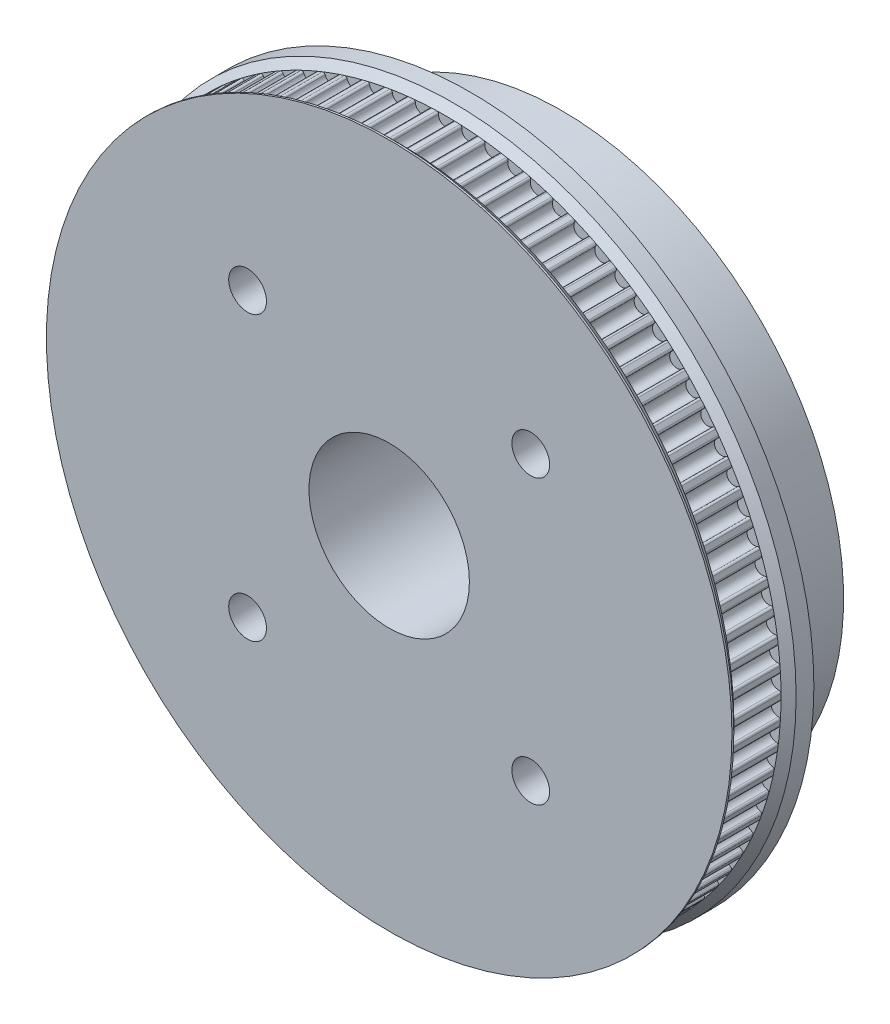
SolidWorks part; units mm, degrees
ref_plane "Front Plane" through (0, 0, 0) normal (0, 0, 1) x (1, 0, 0)
ref_plane "Top Plane" through (0, 0, 0) normal (0, 1, 0) x (1, 0, 0)
ref_plane "Right Plane" through (0, 0, 0) normal (1, 0, 0) x (0, 0, -1)
sketch "Sketch1" plane through (0, 0, 0) normal (0, 0, 1) x (1, 0, 0)
  line L0 (0, 71.6197) -> (0, 0) construction
  line L1 (0, 0) -> (4.9959, 71.4453) construction
  line L2 (0, 70.4947) -> (1.9534, 70.5727) construction
  line L3 (2.9742, 70.537) -> (4.9175, 70.323) construction
  line L4 (1.9534, 70.5727) -> (1.9653, 71.0025) construction
  line L5 (2.9742, 70.537) -> (2.9923, 70.9667) construction
  arc A0 (0, 71.6197) -> (4.9959, 71.4453) centre (0, 0) cw construction
  circle A1 centre (0, 0) radius 71.6197 construction
  circle A2 centre (0, 0) radius 71.0297
  circle A3 centre (0, 0) radius 68.9697
  circle A8 centre (0, 0) radius 72.7697 construction
  circle A9 centre (0, 70.4947) radius 1.525
  circle A10 centre (4.9175, 70.323) radius 1.525
  circle A11 centre (1.9534, 70.5727) radius 0.43
  circle A12 centre (2.9742, 70.537) radius 0.43
  point P18 (0, 68.9697)
  point P19 (4.2572, 15.8881)
  point P20 (4.2572, 15.8881)
  point P21 (1.5238, 70.5555)
  point P23 (3.4016, 70.49)
  dimension "D6" = 3.05
  dimension "D7" = 3.05
  dimension "D8" = 0.86
  dimension "D9" = 0.86
  dimension "D5" = 3.8
  dimension "D2" = 5
  dimension "D3" = 0.59
  dimension "D4" = 2.06
extrude "Boss-Extrude1" add sketch "Sketch1" along normal blind 10 contours A2
extrude "Cut-Extrude1" cut sketch "Sketch1<5>" along normal through all contours A11 A2 A9 | A12 A10 A2 | A9 | A10 region at (3.3605, 70.8449, 0) region at (1.5896, 70.9067, 0)
sketch "Sketch1<5>" plane through (0, 0, 0) normal (0, 0, 1) x (1, 0, 0) same geometry as "Sketch1"
pattern_circular "CirPattern3" count 90 over 360 about axis through (0, 0, 10) along (0, 0, 1) of "Cut-Extrude1"
sketch "Sketch2" plane through (0, 0, 10) normal (0, 0, 1) x (1, 0, 0)
  circle A0 centre (0, 0) radius 72.7697 construction
  arc A81 (-46.5195, 53.0692) -> (-44.1849, 55.0282) centre (-45.3131, 54.0021) ccw
  arc A82 (-46.5195, 53.0692) -> (-44.1849, 55.0282) centre (-45.3131, 54.0021) ccw
  arc A83 (-46.5195, 53.0692) -> (-47.1451, 53.1278) centre (-46.8597, 52.8062) ccw
  arc A84 (-46.5195, 53.0692) -> (-47.1451, 53.1278) centre (-46.8597, 52.8062) ccw
  arc A85 (-47.1451, 53.1278) -> (-47.9088, 52.4402) centre (0, 0) ccw
  arc A86 (-47.1451, 53.1278) -> (-47.9088, 52.4402) centre (0, 0) ccw
  arc A87 (-47.9088, 52.4402) -> (-47.9159, 51.8119) centre (-47.6187, 52.1227) ccw
  arc A88 (-47.9088, 52.4402) -> (-47.9159, 51.8119) centre (-47.6187, 52.1227) ccw
  arc A89 (-50.1081, 49.6949) -> (-47.9159, 51.8119) centre (-48.9698, 50.7097) ccw
  arc A90 (-50.1081, 49.6949) -> (-47.9159, 51.8119) centre (-48.9698, 50.7097) ccw
  arc A91 (-50.1081, 49.6949) -> (-50.7363, 49.7097) centre (-50.4291, 49.4088) ccw
  arc A92 (-50.1081, 49.6949) -> (-50.7363, 49.7097) centre (-50.4291, 49.4088) ccw
  arc A93 (-50.7363, 49.7097) -> (-51.4501, 48.9705) centre (0, 0) ccw
  arc A95 (-50.7363, 49.7097) -> (-51.4501, 48.9705) centre (0, 0) ccw
  arc A97 (-51.4501, 48.9705) -> (-51.4134, 48.3433) centre (-51.1386, 48.674) ccw
  arc A99 (-51.4501, 48.9705) -> (-51.4134, 48.3433) centre (-51.1386, 48.674) ccw
  arc A101 (-53.4526, 46.0785) -> (-51.4134, 48.3433) centre (-52.3878, 47.1702) ccw
  arc A103 (-53.4526, 46.0785) -> (-51.4134, 48.3433) centre (-52.3878, 47.1702) ccw
  arc A105 (-53.4526, 46.0785) -> (-54.0802, 46.0494) centre (-53.7528, 45.7707) ccw
  arc A107 (-53.4526, 46.0785) -> (-54.0802, 46.0494) centre (-53.7528, 45.7707) ccw
  arc A109 (-54.0802, 46.0494) -> (-54.7408, 45.2622) centre (0, 0) ccw
  arc A111 (-54.0802, 46.0494) -> (-54.7408, 45.2622) centre (0, 0) ccw
  arc A112 (-54.7408, 45.2622) -> (-54.6604, 44.6391) centre (-54.4094, 44.9882) ccw
  arc A114 (-54.7408, 45.2622) -> (-54.6604, 44.6391) centre (-54.4094, 44.9882) ccw
  arc A116 (-56.5367, 42.2376) -> (-54.6604, 44.6391) centre (-55.5506, 43.4009) ccw
  arc A118 (-56.5367, 42.2376) -> (-54.6604, 44.6391) centre (-55.5506, 43.4009) ccw
  arc A122 (-56.5367, 42.2376) -> (-57.1607, 42.1648) centre (-56.8147, 41.9096) ccw
  arc A126 (-56.5367, 42.2376) -> (-57.1607, 42.1648) centre (-56.8147, 41.9096) ccw
  arc A130 (-57.1607, 42.1648) -> (-57.7648, 41.3335) centre (0, 0) ccw
  arc A134 (-57.1607, 42.1648) -> (-57.7648, 41.3335) centre (0, 0) ccw
  arc A138 (-57.7648, 41.3335) -> (-57.6411, 40.7174) centre (-57.4151, 41.0832) ccw
  arc A142 (-57.7648, 41.3335) -> (-57.6411, 40.7174) centre (-57.4151, 41.0832) ccw
  arc A146 (-59.3453, 38.1909) -> (-57.6411, 40.7174) centre (-58.4428, 39.4201) ccw
  arc A150 (-59.3453, 38.1909) -> (-57.6411, 40.7174) centre (-58.4428, 39.4201) ccw
  arc A154 (-59.3453, 38.1909) -> (-59.9628, 38.0748) centre (-59.5998, 37.8443) ccw
  arc A158 (-59.3453, 38.1909) -> (-59.9628, 38.0748) centre (-59.5998, 37.8443) ccw
  arc A162 (-59.9628, 38.0748) -> (-60.5073, 37.2033) centre (0, 0) ccw
  arc A166 (-59.9628, 38.0748) -> (-60.5073, 37.2033) centre (0, 0) ccw
  arc A170 (-60.5073, 37.2033) -> (-60.341, 36.5974) centre (-60.141, 36.9781) ccw
  arc A174 (-60.5073, 37.2033) -> (-60.341, 36.5974) centre (-60.141, 36.9781) ccw
  arc A178 (-61.8648, 33.9581) -> (-60.341, 36.5974) centre (-61.0502, 35.2474) ccw
  arc A182 (-61.8648, 33.9581) -> (-60.341, 36.5974) centre (-61.0502, 35.2474) ccw
  arc A186 (-61.8648, 33.9581) -> (-62.4727, 33.7992) centre (-62.0945, 33.5946) ccw
  arc A190 (-61.8648, 33.9581) -> (-62.4727, 33.7992) centre (-62.0945, 33.5946) ccw
  arc A193 (-62.4727, 33.7992) -> (-62.9551, 32.8919) centre (0, 0) ccw
  arc A195 (-62.4727, 33.7992) -> (-62.9551, 32.8919) centre (0, 0) ccw
  arc A197 (-62.9551, 32.8919) -> (-62.7469, 32.2991) centre (-62.574, 32.6928) ccw
  arc A199 (-62.9551, 32.8919) -> (-62.7469, 32.2991) centre (-62.574, 32.6928) ccw
  arc A201 (-64.0829, 29.5599) -> (-62.7469, 32.2991) centre (-63.3602, 30.9029) ccw
  arc A203 (-64.0829, 29.5599) -> (-62.7469, 32.2991) centre (-63.3602, 30.9029) ccw
  arc A205 (-64.0829, 29.5599) -> (-64.6782, 29.359) centre (-64.2867, 29.1813) ccw
  arc A207 (-64.0829, 29.5599) -> (-64.6782, 29.359) centre (-64.2867, 29.1813) ccw
  arc A209 (-64.6782, 29.359) -> (-65.0962, 28.4202) centre (0, 0) ccw
  arc A211 (-64.6782, 29.359) -> (-65.0962, 28.4202) centre (0, 0) ccw
  arc A213 (-65.0962, 28.4202) -> (-64.8471, 27.8434) centre (-64.7021, 28.2482) ccw
  arc A215 (-65.0962, 28.4202) -> (-64.8471, 27.8434) centre (-64.7021, 28.2482) ccw
  arc A217 (-65.9888, 25.0177) -> (-64.8471, 27.8434) centre (-65.3616, 26.4078) ccw
  arc A221 (-65.9888, 25.0177) -> (-64.8471, 27.8434) centre (-65.3616, 26.4078) ccw
  arc A225 (-65.9888, 25.0177) -> (-66.5686, 24.7758) centre (-66.1656, 24.6258) ccw
  arc A229 (-65.9888, 25.0177) -> (-66.5686, 24.7758) centre (-66.1656, 24.6258) ccw
  arc A233 (-66.5686, 24.7758) -> (-66.9201, 23.8101) centre (0, 0) ccw
  arc A241 (-66.5686, 24.7758) -> (-66.9201, 23.8101) centre (0, 0) ccw
  arc A245 (-66.9201, 23.8101) -> (-66.6314, 23.2521) centre (-66.515, 23.666) ccw
  arc A247 (-66.9201, 23.8101) -> (-66.6314, 23.2521) centre (-66.515, 23.666) ccw
  arc A249 (-67.5732, 20.3537) -> (-66.6314, 23.2521) centre (-67.0445, 21.7841) ccw
  arc A251 (-67.5732, 20.3537) -> (-66.6314, 23.2521) centre (-67.0445, 21.7841) ccw
  arc A253 (-67.5732, 20.3537) -> (-68.1347, 20.0718) centre (-67.7223, 19.9503) ccw
  arc A255 (-67.5732, 20.3537) -> (-68.1347, 20.0718) centre (-67.7223, 19.9503) ccw
  arc A257 (-68.1347, 20.0718) -> (-68.418, 19.084) centre (0, 0) ccw
  arc A259 (-68.1347, 20.0718) -> (-68.418, 19.084) centre (0, 0) ccw
  arc A261 (-68.418, 19.084) -> (-68.0911, 18.5475) centre (-68.0038, 18.9685) ccw
  arc A263 (-68.418, 19.084) -> (-68.0911, 18.5475) centre (-68.0038, 18.9685) ccw
  arc A373 (3.4016, 70.49) -> (6.4418, 70.2774) centre (4.9175, 70.323) ccw
  arc A374 (3.4016, 70.49) -> (2.9923, 70.9667) centre (2.9742, 70.537) ccw
  arc A375 (2.9923, 70.9667) -> (1.9653, 71.0025) centre (0, 0) ccw
  arc A376 (1.9653, 71.0025) -> (1.5238, 70.5555) centre (1.9534, 70.5727) ccw
  arc A377 (-1.5238, 70.5555) -> (1.5238, 70.5555) centre (0, 70.4947) ccw
  arc A378 (-1.5238, 70.5555) -> (-1.9653, 71.0025) centre (-1.9534, 70.5727) ccw
  arc A379 (-1.9653, 71.0025) -> (-2.9923, 70.9667) centre (0, 0) ccw
  arc A380 (-2.9923, 70.9667) -> (-3.4016, 70.49) centre (-2.9742, 70.537) ccw
  arc A381 (-6.4418, 70.2774) -> (-3.4016, 70.49) centre (-4.9175, 70.323) ccw
  arc A382 (-6.4418, 70.2774) -> (-6.9134, 70.6925) centre (-6.8716, 70.2645) ccw
  arc A383 (-6.9134, 70.6925) -> (-7.9354, 70.5851) centre (0, 0) ccw
  arc A384 (-7.9354, 70.5851) -> (-8.3105, 70.081) centre (-7.8874, 70.1578) ccw
  arc A385 (-11.3284, 69.6568) -> (-8.3105, 70.081) centre (-9.811, 69.8087) ccw
  arc A386 (-11.3284, 69.6568) -> (-11.8279, 70.038) centre (-11.7563, 69.614) ccw
  arc A387 (-11.8279, 70.038) -> (-12.8399, 69.8596) centre (0, 0) ccw
  arc A388 (-12.8399, 69.8596) -> (-13.1788, 69.3305) centre (-12.7621, 69.4367) ccw
  arc A389 (-16.1598, 68.6969) -> (-13.1788, 69.3305) centre (-14.6567, 68.9542) ccw
  arc A390 (-16.1598, 68.6969) -> (-16.6847, 69.0423) centre (-16.5836, 68.6244) ccw
  arc A391 (-16.6847, 69.0423) -> (-17.6817, 68.7937) centre (0, 0) ccw
  arc A392 (-17.6817, 68.7937) -> (-17.983, 68.2424) centre (-17.5747, 68.3773) ccw
  arc A393 (-20.9125, 67.4023) -> (-17.983, 68.2424) centre (-19.431, 67.7639) ccw
  arc A394 (-20.9125, 67.4023) -> (-21.4602, 67.7103) centre (-21.3302, 67.3004) ccw
  arc A395 (-21.4602, 67.7103) -> (-22.4375, 67.3927) centre (0, 0) ccw
  arc A396 (-22.4375, 67.3927) -> (-22.6995, 66.8217) centre (-22.3016, 66.9848) ccw
  arc A397 (-25.5633, 65.7794) -> (-22.6995, 66.8217) centre (-24.1106, 66.2434) ccw
  arc A398 (-25.5633, 65.7794) -> (-26.1311, 66.0484) centre (-25.9729, 65.6485) ccw
  arc A399 (-26.1311, 66.0484) -> (-27.0839, 65.6634) centre (0, 0) ccw
  arc A400 (-27.0839, 65.6634) -> (-27.3055, 65.0755) centre (-26.9199, 65.2659) ccw
  arc A401 (-30.0896, 63.8359) -> (-27.3055, 65.0755) centre (-28.6728, 64.4001) ccw
  arc A402 (-30.0896, 63.8359) -> (-30.6748, 64.0647) centre (-30.4891, 63.6768) ccw
  arc A403 (-30.6748, 64.0647) -> (-31.5984, 63.6142) centre (0, 0) ccw
  arc A404 (-31.5984, 63.6142) -> (-31.7784, 63.0122) centre (-31.4071, 63.2291) ccw
  arc A405 (-34.4692, 61.5815) -> (-31.7784, 63.0122) centre (-33.0953, 62.2431) ccw
  arc A406 (-34.4692, 61.5815) -> (-35.069, 61.7688) centre (-34.8567, 61.3949) ccw
  arc A407 (-35.069, 61.7688) -> (-35.9589, 61.255) centre (0, 0) ccw
  arc A408 (-35.9589, 61.255) -> (-36.0965, 60.642) centre (-35.7412, 60.8842) ccw
  arc A409 (-38.681, 59.027) -> (-36.0965, 60.642) centre (-37.3565, 59.7829) ccw
  arc A410 (-38.681, 59.027) -> (-39.2923, 59.1721) centre (-39.0544, 58.8139) ccw
  arc A411 (-39.2923, 59.1721) -> (-40.1442, 58.5975) centre (0, 0) ccw
  arc A412 (-40.1442, 58.5975) -> (-40.2387, 57.9763) centre (-39.9012, 58.2427) ccw
  arc A413 (-42.7043, 56.185) -> (-40.2387, 57.9763) centre (-41.4358, 57.0314) ccw
  arc A414 (-42.7043, 56.185) -> (-43.3242, 56.2871) centre (-43.062, 55.9463) ccw
  arc A415 (-43.3242, 56.2871) -> (-44.134, 55.6544) centre (0, 0) ccw
  arc A416 (-44.134, 55.6544) -> (-44.1849, 55.0282) centre (-43.8668, 55.3175) ccw
  arc A649 (3.4016, 70.49) -> (6.4418, 70.2774) centre (4.9175, 70.323) ccw
  arc A650 (3.4016, 70.49) -> (2.9923, 70.9667) centre (2.9742, 70.537) ccw
  arc A651 (2.9923, 70.9667) -> (1.9653, 71.0025) centre (0, 0) ccw
  arc A652 (1.9653, 71.0025) -> (1.5238, 70.5555) centre (1.9534, 70.5727) ccw
  arc A653 (-1.5238, 70.5555) -> (1.5238, 70.5555) centre (0, 70.4947) ccw
  arc A654 (-1.5238, 70.5555) -> (-1.9653, 71.0025) centre (-1.9534, 70.5727) ccw
  arc A655 (-1.9653, 71.0025) -> (-2.9923, 70.9667) centre (0, 0) ccw
  arc A656 (-2.9923, 70.9667) -> (-3.4016, 70.49) centre (-2.9742, 70.537) ccw
  arc A657 (-6.4418, 70.2774) -> (-3.4016, 70.49) centre (-4.9175, 70.323) ccw
  arc A658 (-6.4418, 70.2774) -> (-6.9134, 70.6925) centre (-6.8716, 70.2645) ccw
  arc A659 (-6.9134, 70.6925) -> (-7.9354, 70.5851) centre (0, 0) ccw
  arc A660 (-7.9354, 70.5851) -> (-8.3105, 70.081) centre (-7.8874, 70.1578) ccw
  arc A661 (-11.3284, 69.6568) -> (-8.3105, 70.081) centre (-9.811, 69.8087) ccw
  arc A662 (-11.3284, 69.6568) -> (-11.8279, 70.038) centre (-11.7563, 69.614) ccw
  arc A663 (-11.8279, 70.038) -> (-12.8399, 69.8596) centre (0, 0) ccw
  arc A664 (-12.8399, 69.8596) -> (-13.1788, 69.3305) centre (-12.7621, 69.4367) ccw
  arc A665 (-16.1598, 68.6969) -> (-13.1788, 69.3305) centre (-14.6567, 68.9542) ccw
  arc A666 (-16.1598, 68.6969) -> (-16.6847, 69.0423) centre (-16.5836, 68.6244) ccw
  arc A667 (-16.6847, 69.0423) -> (-17.6817, 68.7937) centre (0, 0) ccw
  arc A668 (-17.6817, 68.7937) -> (-17.983, 68.2424) centre (-17.5747, 68.3773) ccw
  arc A669 (-20.9125, 67.4023) -> (-17.983, 68.2424) centre (-19.431, 67.7639) ccw
  arc A670 (-20.9125, 67.4023) -> (-21.4602, 67.7103) centre (-21.3302, 67.3004) ccw
  arc A671 (-21.4602, 67.7103) -> (-22.4375, 67.3927) centre (0, 0) ccw
  arc A672 (-22.4375, 67.3927) -> (-22.6995, 66.8217) centre (-22.3016, 66.9848) ccw
  arc A673 (-25.5633, 65.7794) -> (-22.6995, 66.8217) centre (-24.1106, 66.2434) ccw
  arc A674 (-25.5633, 65.7794) -> (-26.1311, 66.0484) centre (-25.9729, 65.6485) ccw
  arc A675 (-26.1311, 66.0484) -> (-27.0839, 65.6634) centre (0, 0) ccw
  arc A676 (-27.0839, 65.6634) -> (-27.3055, 65.0755) centre (-26.9199, 65.2659) ccw
  arc A677 (-30.0896, 63.8359) -> (-27.3055, 65.0755) centre (-28.6728, 64.4001) ccw
  arc A678 (-30.0896, 63.8359) -> (-30.6748, 64.0647) centre (-30.4891, 63.6768) ccw
  arc A679 (-30.6748, 64.0647) -> (-31.5984, 63.6142) centre (0, 0) ccw
  arc A680 (-31.5984, 63.6142) -> (-31.7784, 63.0122) centre (-31.4071, 63.2291) ccw
  arc A681 (-34.4692, 61.5815) -> (-31.7784, 63.0122) centre (-33.0953, 62.2431) ccw
  arc A682 (-34.4692, 61.5815) -> (-35.069, 61.7688) centre (-34.8567, 61.3949) ccw
  arc A683 (-35.069, 61.7688) -> (-35.9589, 61.255) centre (0, 0) ccw
  arc A684 (-35.9589, 61.255) -> (-36.0965, 60.642) centre (-35.7412, 60.8842) ccw
  arc A685 (-38.681, 59.027) -> (-36.0965, 60.642) centre (-37.3565, 59.7829) ccw
  arc A686 (-38.681, 59.027) -> (-39.2923, 59.1721) centre (-39.0544, 58.8139) ccw
  arc A687 (-39.2923, 59.1721) -> (-40.1442, 58.5975) centre (0, 0) ccw
  arc A688 (-40.1442, 58.5975) -> (-40.2387, 57.9763) centre (-39.9012, 58.2427) ccw
  arc A689 (-42.7043, 56.185) -> (-40.2387, 57.9763) centre (-41.4358, 57.0314) ccw
  arc A690 (-42.7043, 56.185) -> (-43.3242, 56.2871) centre (-43.062, 55.9463) ccw
  arc A691 (-43.3242, 56.2871) -> (-44.134, 55.6544) centre (0, 0) ccw
  arc A692 (-44.134, 55.6544) -> (-44.1849, 55.0282) centre (-43.8668, 55.3175) ccw
  arc A1359 (-6.9134, -70.6925) -> (-6.4418, -70.2774) centre (-6.8716, -70.2645) ccw
  arc A1361 (-6.9134, -70.6925) -> (-6.4418, -70.2774) centre (-6.8716, -70.2645) ccw
  arc A1363 (-3.4016, -70.49) -> (-6.4418, -70.2774) centre (-4.9175, -70.323) ccw
  arc A1365 (-3.4016, -70.49) -> (-6.4418, -70.2774) centre (-4.9175, -70.323) ccw
  arc A1367 (-3.4016, -70.49) -> (-2.9923, -70.9667) centre (-2.9742, -70.537) ccw
  arc A1369 (-3.4016, -70.49) -> (-2.9923, -70.9667) centre (-2.9742, -70.537) ccw
  arc A1371 (-2.9923, -70.9667) -> (-1.9653, -71.0025) centre (0, 0) ccw
  arc A1373 (-2.9923, -70.9667) -> (-1.9653, -71.0025) centre (0, 0) ccw
  arc A1375 (-1.9653, -71.0025) -> (-1.5238, -70.5555) centre (-1.9534, -70.5727) ccw
  arc A1377 (-1.9653, -71.0025) -> (-1.5238, -70.5555) centre (-1.9534, -70.5727) ccw
  arc A1379 (1.5238, -70.5555) -> (-1.5238, -70.5555) centre (0, -70.4947) ccw
  arc A1381 (1.5238, -70.5555) -> (-1.5238, -70.5555) centre (0, -70.4947) ccw
  arc A1383 (1.5238, -70.5555) -> (1.9653, -71.0025) centre (1.9534, -70.5727) ccw
  arc A1385 (1.5238, -70.5555) -> (1.9653, -71.0025) centre (1.9534, -70.5727) ccw
  arc A1387 (1.9653, -71.0025) -> (2.9923, -70.9667) centre (0, 0) ccw
  arc A1389 (1.9653, -71.0025) -> (2.9923, -70.9667) centre (0, 0) ccw
  arc A1391 (2.9923, -70.9667) -> (3.4016, -70.49) centre (2.9742, -70.537) ccw
  arc A1393 (2.9923, -70.9667) -> (3.4016, -70.49) centre (2.9742, -70.537) ccw
  arc A1395 (6.4418, -70.2774) -> (3.4016, -70.49) centre (4.9175, -70.323) ccw
  arc A1397 (6.4418, -70.2774) -> (3.4016, -70.49) centre (4.9175, -70.323) ccw
  arc A1399 (6.4418, -70.2774) -> (6.9134, -70.6925) centre (6.8716, -70.2645) ccw
  arc A1401 (6.4418, -70.2774) -> (6.9134, -70.6925) centre (6.8716, -70.2645) ccw
  arc A1403 (6.9134, -70.6925) -> (7.9354, -70.5851) centre (0, 0) ccw
  arc A1405 (6.9134, -70.6925) -> (7.9354, -70.5851) centre (0, 0) ccw
  arc A1407 (7.9354, -70.5851) -> (8.3105, -70.081) centre (7.8874, -70.1578) ccw
  arc A1409 (7.9354, -70.5851) -> (8.3105, -70.081) centre (7.8874, -70.1578) ccw
  arc A1411 (11.3284, -69.6568) -> (8.3105, -70.081) centre (9.811, -69.8087) ccw
  arc A1413 (11.3284, -69.6568) -> (8.3105, -70.081) centre (9.811, -69.8087) ccw
  arc A1415 (11.3284, -69.6568) -> (11.8279, -70.038) centre (11.7563, -69.614) ccw
  arc A1417 (11.3284, -69.6568) -> (11.8279, -70.038) centre (11.7563, -69.614) ccw
  arc A1419 (11.8279, -70.038) -> (12.8399, -69.8596) centre (0, 0) ccw
  arc A1421 (11.8279, -70.038) -> (12.8399, -69.8596) centre (0, 0) ccw
  arc A1423 (12.8399, -69.8596) -> (13.1788, -69.3305) centre (12.7621, -69.4367) ccw
  arc A1425 (12.8399, -69.8596) -> (13.1788, -69.3305) centre (12.7621, -69.4367) ccw
  arc A1427 (16.1598, -68.6969) -> (13.1788, -69.3305) centre (14.6567, -68.9542) ccw
  arc A1429 (16.1598, -68.6969) -> (13.1788, -69.3305) centre (14.6567, -68.9542) ccw
  arc A1431 (16.1598, -68.6969) -> (16.6847, -69.0423) centre (16.5836, -68.6244) ccw
  arc A1433 (16.1598, -68.6969) -> (16.6847, -69.0423) centre (16.5836, -68.6244) ccw
  arc A1435 (16.6847, -69.0423) -> (17.6817, -68.7937) centre (0, 0) ccw
  arc A1437 (16.6847, -69.0423) -> (17.6817, -68.7937) centre (0, 0) ccw
  arc A1439 (17.6817, -68.7937) -> (17.983, -68.2424) centre (17.5747, -68.3773) ccw
  arc A1441 (17.6817, -68.7937) -> (17.983, -68.2424) centre (17.5747, -68.3773) ccw
  arc A1443 (20.9125, -67.4023) -> (17.983, -68.2424) centre (19.431, -67.7639) ccw
  arc A1445 (20.9125, -67.4023) -> (17.983, -68.2424) centre (19.431, -67.7639) ccw
  arc A1447 (20.9125, -67.4023) -> (21.4602, -67.7103) centre (21.3302, -67.3004) ccw
  arc A1449 (20.9125, -67.4023) -> (21.4602, -67.7103) centre (21.3302, -67.3004) ccw
  arc A1451 (21.4602, -67.7103) -> (22.4375, -67.3927) centre (0, 0) ccw
  arc A1453 (21.4602, -67.7103) -> (22.4375, -67.3927) centre (0, 0) ccw
  arc A1455 (22.4375, -67.3927) -> (22.6995, -66.8217) centre (22.3016, -66.9848) ccw
  arc A1457 (22.4375, -67.3927) -> (22.6995, -66.8217) centre (22.3016, -66.9848) ccw
  arc A1459 (25.5633, -65.7794) -> (22.6995, -66.8217) centre (24.1106, -66.2434) ccw
  arc A1461 (25.5633, -65.7794) -> (22.6995, -66.8217) centre (24.1106, -66.2434) ccw
  arc A1463 (25.5633, -65.7794) -> (26.1311, -66.0484) centre (25.9729, -65.6485) ccw
  arc A1465 (25.5633, -65.7794) -> (26.1311, -66.0484) centre (25.9729, -65.6485) ccw
  arc A1467 (26.1311, -66.0484) -> (27.0839, -65.6634) centre (0, 0) ccw
  arc A1469 (26.1311, -66.0484) -> (27.0839, -65.6634) centre (0, 0) ccw
  arc A1471 (27.0839, -65.6634) -> (27.3055, -65.0755) centre (26.9199, -65.2659) ccw
  arc A1473 (27.0839, -65.6634) -> (27.3055, -65.0755) centre (26.9199, -65.2659) ccw
  arc A1475 (30.0896, -63.8359) -> (27.3055, -65.0755) centre (28.6728, -64.4001) ccw
  arc A1477 (30.0896, -63.8359) -> (27.3055, -65.0755) centre (28.6728, -64.4001) ccw
  arc A1479 (30.0896, -63.8359) -> (30.6748, -64.0647) centre (30.4891, -63.6768) ccw
  arc A1481 (30.0896, -63.8359) -> (30.6748, -64.0647) centre (30.4891, -63.6768) ccw
  arc A1483 (30.6748, -64.0647) -> (31.5984, -63.6142) centre (0, 0) ccw
  arc A1485 (30.6748, -64.0647) -> (31.5984, -63.6142) centre (0, 0) ccw
  arc A1487 (31.5984, -63.6142) -> (31.7784, -63.0122) centre (31.4071, -63.2291) ccw
  arc A1489 (31.5984, -63.6142) -> (31.7784, -63.0122) centre (31.4071, -63.2291) ccw
  arc A1491 (34.4692, -61.5815) -> (31.7784, -63.0122) centre (33.0953, -62.2431) ccw
  arc A1493 (34.4692, -61.5815) -> (31.7784, -63.0122) centre (33.0953, -62.2431) ccw
  arc A1495 (34.4692, -61.5815) -> (35.069, -61.7688) centre (34.8567, -61.3949) ccw
  arc A1497 (34.4692, -61.5815) -> (35.069, -61.7688) centre (34.8567, -61.3949) ccw
  arc A1499 (35.069, -61.7688) -> (35.9589, -61.255) centre (0, 0) ccw
  arc A1501 (35.069, -61.7688) -> (35.9589, -61.255) centre (0, 0) ccw
  arc A1503 (35.9589, -61.255) -> (36.0965, -60.642) centre (35.7412, -60.8842) ccw
  arc A1505 (35.9589, -61.255) -> (36.0965, -60.642) centre (35.7412, -60.8842) ccw
  arc A1507 (38.681, -59.027) -> (36.0965, -60.642) centre (37.3565, -59.7829) ccw
  arc A1509 (38.681, -59.027) -> (36.0965, -60.642) centre (37.3565, -59.7829) ccw
  arc A1511 (38.681, -59.027) -> (39.2923, -59.1721) centre (39.0544, -58.8139) ccw
  arc A1513 (38.681, -59.027) -> (39.2923, -59.1721) centre (39.0544, -58.8139) ccw
  arc A1515 (39.2923, -59.1721) -> (40.1442, -58.5975) centre (0, 0) ccw
  arc A1517 (39.2923, -59.1721) -> (40.1442, -58.5975) centre (0, 0) ccw
  arc A1519 (40.1442, -58.5975) -> (40.2387, -57.9763) centre (39.9012, -58.2427) ccw
  arc A1521 (40.1442, -58.5975) -> (40.2387, -57.9763) centre (39.9012, -58.2427) ccw
  arc A1523 (42.7043, -56.185) -> (40.2387, -57.9763) centre (41.4358, -57.0314) ccw
  arc A1525 (42.7043, -56.185) -> (40.2387, -57.9763) centre (41.4358, -57.0314) ccw
  arc A1527 (42.7043, -56.185) -> (43.3242, -56.2871) centre (43.062, -55.9463) ccw
  arc A1529 (42.7043, -56.185) -> (43.3242, -56.2871) centre (43.062, -55.9463) ccw
  arc A1531 (43.3242, -56.2871) -> (44.134, -55.6544) centre (0, 0) ccw
  arc A1533 (43.3242, -56.2871) -> (44.134, -55.6544) centre (0, 0) ccw
  arc A1535 (44.134, -55.6544) -> (44.1849, -55.0282) centre (43.8668, -55.3175) ccw
  arc A1537 (44.134, -55.6544) -> (44.1849, -55.0282) centre (43.8668, -55.3175) ccw
  arc A1539 (46.5195, -53.0692) -> (44.1849, -55.0282) centre (45.3131, -54.0021) ccw
  arc A1541 (46.5195, -53.0692) -> (44.1849, -55.0282) centre (45.3131, -54.0021) ccw
  arc A1543 (46.5195, -53.0692) -> (47.1451, -53.1278) centre (46.8597, -52.8062) ccw
  arc A1545 (46.5195, -53.0692) -> (47.1451, -53.1278) centre (46.8597, -52.8062) ccw
  arc A1547 (47.1451, -53.1278) -> (47.9088, -52.4402) centre (0, 0) ccw
  arc A1549 (47.1451, -53.1278) -> (47.9088, -52.4402) centre (0, 0) ccw
  arc A1551 (47.9088, -52.4402) -> (47.9159, -51.8119) centre (47.6187, -52.1227) ccw
  arc A1553 (47.9088, -52.4402) -> (47.9159, -51.8119) centre (47.6187, -52.1227) ccw
  arc A1555 (50.1081, -49.6949) -> (47.9159, -51.8119) centre (48.9698, -50.7097) ccw
  arc A1557 (50.1081, -49.6949) -> (47.9159, -51.8119) centre (48.9698, -50.7097) ccw
  arc A1559 (50.1081, -49.6949) -> (50.7363, -49.7097) centre (50.4291, -49.4088) ccw
  arc A1561 (50.1081, -49.6949) -> (50.7363, -49.7097) centre (50.4291, -49.4088) ccw
  arc A1563 (50.7363, -49.7097) -> (51.4501, -48.9705) centre (0, 0) ccw
  arc A1565 (50.7363, -49.7097) -> (51.4501, -48.9705) centre (0, 0) ccw
  arc A1567 (51.4501, -48.9705) -> (51.4134, -48.3433) centre (51.1386, -48.674) ccw
  arc A1569 (51.4501, -48.9705) -> (51.4134, -48.3433) centre (51.1386, -48.674) ccw
  arc A1571 (53.4526, -46.0785) -> (51.4134, -48.3433) centre (52.3878, -47.1702) ccw
  arc A1573 (53.4526, -46.0785) -> (51.4134, -48.3433) centre (52.3878, -47.1702) ccw
  arc A1575 (53.4526, -46.0785) -> (54.0802, -46.0494) centre (53.7528, -45.7707) ccw
  arc A1577 (53.4526, -46.0785) -> (54.0802, -46.0494) centre (53.7528, -45.7707) ccw
  arc A1579 (54.0802, -46.0494) -> (54.7408, -45.2622) centre (0, 0) ccw
  arc A1581 (54.0802, -46.0494) -> (54.7408, -45.2622) centre (0, 0) ccw
  arc A1583 (54.7408, -45.2622) -> (54.6604, -44.6391) centre (54.4094, -44.9882) ccw
  arc A1585 (54.7408, -45.2622) -> (54.6604, -44.6391) centre (54.4094, -44.9882) ccw
  arc A1587 (56.5367, -42.2376) -> (54.6604, -44.6391) centre (55.5506, -43.4009) ccw
  arc A1589 (56.5367, -42.2376) -> (54.6604, -44.6391) centre (55.5506, -43.4009) ccw
  arc A1591 (56.5367, -42.2376) -> (57.1607, -42.1648) centre (56.8147, -41.9096) ccw
  arc A1593 (56.5367, -42.2376) -> (57.1607, -42.1648) centre (56.8147, -41.9096) ccw
  arc A1595 (57.1607, -42.1648) -> (57.7648, -41.3335) centre (0, 0) ccw
  arc A1596 (57.1607, -42.1648) -> (57.7648, -41.3335) centre (0, 0) ccw
  arc A1597 (57.7648, -41.3335) -> (57.6411, -40.7174) centre (57.4151, -41.0832) ccw
  arc A1598 (57.7648, -41.3335) -> (57.6411, -40.7174) centre (57.4151, -41.0832) ccw
  arc A1599 (59.3453, -38.1909) -> (57.6411, -40.7174) centre (58.4428, -39.4201) ccw
  arc A1600 (59.3453, -38.1909) -> (57.6411, -40.7174) centre (58.4428, -39.4201) ccw
  arc A1601 (59.3453, -38.1909) -> (59.9628, -38.0748) centre (59.5998, -37.8443) ccw
  arc A1602 (59.3453, -38.1909) -> (59.9628, -38.0748) centre (59.5998, -37.8443) ccw
  arc A1603 (59.9628, -38.0748) -> (60.5073, -37.2033) centre (0, 0) ccw
  arc A1604 (59.9628, -38.0748) -> (60.5073, -37.2033) centre (0, 0) ccw
  arc A1605 (60.5073, -37.2033) -> (60.341, -36.5974) centre (60.141, -36.9781) ccw
  arc A1606 (60.5073, -37.2033) -> (60.341, -36.5974) centre (60.141, -36.9781) ccw
  arc A1607 (61.8648, -33.9581) -> (60.341, -36.5974) centre (61.0502, -35.2474) ccw
  arc A1608 (61.8648, -33.9581) -> (60.341, -36.5974) centre (61.0502, -35.2474) ccw
  arc A1609 (61.8648, -33.9581) -> (62.4727, -33.7992) centre (62.0945, -33.5946) ccw
  arc A1610 (61.8648, -33.9581) -> (62.4727, -33.7992) centre (62.0945, -33.5946) ccw
  arc A1611 (62.4727, -33.7992) -> (62.9551, -32.8919) centre (0, 0) ccw
  arc A1612 (62.4727, -33.7992) -> (62.9551, -32.8919) centre (0, 0) ccw
  arc A1613 (62.9551, -32.8919) -> (62.7469, -32.2991) centre (62.574, -32.6928) ccw
  arc A1614 (62.9551, -32.8919) -> (62.7469, -32.2991) centre (62.574, -32.6928) ccw
  arc A1615 (64.0829, -29.5599) -> (62.7469, -32.2991) centre (63.3602, -30.9029) ccw
  arc A1616 (64.0829, -29.5599) -> (62.7469, -32.2991) centre (63.3602, -30.9029) ccw
  arc A1617 (64.0829, -29.5599) -> (64.6782, -29.359) centre (64.2867, -29.1813) ccw
  arc A1618 (64.0829, -29.5599) -> (64.6782, -29.359) centre (64.2867, -29.1813) ccw
  arc A1619 (64.6782, -29.359) -> (65.0962, -28.4202) centre (0, 0) ccw
  arc A1620 (64.6782, -29.359) -> (65.0962, -28.4202) centre (0, 0) ccw
  arc A1621 (65.0962, -28.4202) -> (64.8471, -27.8434) centre (64.7021, -28.2482) ccw
  arc A1622 (65.0962, -28.4202) -> (64.8471, -27.8434) centre (64.7021, -28.2482) ccw
  arc A1623 (65.9888, -25.0177) -> (64.8471, -27.8434) centre (65.3616, -26.4078) ccw
  arc A1624 (65.9888, -25.0177) -> (64.8471, -27.8434) centre (65.3616, -26.4078) ccw
  arc A1625 (65.9888, -25.0177) -> (66.5686, -24.7758) centre (66.1656, -24.6258) ccw
  arc A1626 (65.9888, -25.0177) -> (66.5686, -24.7758) centre (66.1656, -24.6258) ccw
  arc A1627 (66.5686, -24.7758) -> (66.9201, -23.8101) centre (0, 0) ccw
  arc A1628 (66.5686, -24.7758) -> (66.9201, -23.8101) centre (0, 0) ccw
  arc A1629 (66.9201, -23.8101) -> (66.6314, -23.2521) centre (66.515, -23.666) ccw
  arc A1630 (66.9201, -23.8101) -> (66.6314, -23.2521) centre (66.515, -23.666) ccw
  arc A1631 (67.5732, -20.3537) -> (66.6314, -23.2521) centre (67.0445, -21.7841) ccw
  arc A1632 (67.5732, -20.3537) -> (66.6314, -23.2521) centre (67.0445, -21.7841) ccw
  arc A1633 (67.5732, -20.3537) -> (68.1347, -20.0718) centre (67.7223, -19.9503) ccw
  arc A1634 (67.5732, -20.3537) -> (68.1347, -20.0718) centre (67.7223, -19.9503) ccw
  arc A1635 (68.1347, -20.0718) -> (68.418, -19.084) centre (0, 0) ccw
  arc A1636 (68.1347, -20.0718) -> (68.418, -19.084) centre (0, 0) ccw
  arc A1637 (68.418, -19.084) -> (68.0911, -18.5475) centre (68.0038, -18.9685) ccw
  arc A1638 (68.418, -19.084) -> (68.0911, -18.5475) centre (68.0038, -18.9685) ccw
  arc A1639 (68.8284, -15.5904) -> (68.0911, -18.5475) centre (68.4007, -17.0542) ccw
  arc A1640 (68.8284, -15.5904) -> (68.0911, -18.5475) centre (68.4007, -17.0542) ccw
  arc A1641 (68.8284, -15.5904) -> (69.3689, -15.2701) centre (68.949, -15.1777) ccw
  arc A1642 (68.8284, -15.5904) -> (69.3689, -15.2701) centre (68.949, -15.1777) ccw
  arc A1643 (69.3689, -15.2701) -> (69.5826, -14.2649) centre (0, 0) ccw
  arc A1644 (69.3689, -15.2701) -> (69.5826, -14.2649) centre (0, 0) ccw
  arc A1645 (69.5826, -14.2649) -> (69.219, -13.7525) centre (69.1613, -14.1786) ccw
  arc A1646 (69.5826, -14.2649) -> (69.219, -13.7525) centre (69.1613, -14.1786) ccw
  arc A1647 (69.7483, -10.7512) -> (69.219, -13.7525) centre (69.4238, -12.2413) ccw
  arc A1648 (69.7483, -10.7512) -> (69.219, -13.7525) centre (69.4238, -12.2413) ccw
  arc A1649 (69.7483, -10.7512) -> (70.2651, -10.394) centre (69.8397, -10.3311) ccw
  arc A1650 (69.7483, -10.7512) -> (70.2651, -10.394) centre (69.8397, -10.3311) ccw
  arc A1651 (70.2651, -10.394) -> (70.4081, -9.3764) centre (0, 0) ccw
  arc A1652 (70.2651, -10.394) -> (70.4081, -9.3764) centre (0, 0) ccw
  arc A1653 (70.4081, -9.3764) -> (70.0098, -8.8905) centre (69.9819, -9.3196) ccw
  arc A1654 (70.4081, -9.3764) -> (70.0098, -8.8905) centre (69.9819, -9.3196) ccw
  arc A1655 (70.3283, -5.8596) -> (70.0098, -8.8905) centre (70.1085, -7.3687) ccw
  arc A1656 (70.3283, -5.8596) -> (70.0098, -8.8905) centre (70.1085, -7.3687) ccw
  arc A1657 (70.3283, -5.8596) -> (70.819, -5.4672) centre (70.3903, -5.4341) ccw
  arc A1658 (70.3283, -5.8596) -> (70.819, -5.4672) centre (70.3903, -5.4341) ccw
  arc A1659 (70.819, -5.4672) -> (70.8907, -4.4421) centre (0, 0) ccw
  arc A1660 (70.819, -5.4672) -> (70.8907, -4.4421) centre (0, 0) ccw
  arc A1661 (70.8907, -4.4421) -> (70.4594, -3.9852) centre (70.4615, -4.4152) ccw
  arc A1662 (70.8907, -4.4421) -> (70.4594, -3.9852) centre (70.4615, -4.4152) ccw
  arc A1663 (70.5657, -0.9395) -> (70.4594, -3.9852) centre (70.4518, -2.4602) ccw
  arc A1664 (70.5657, -0.9395) -> (70.4594, -3.9852) centre (70.4518, -2.4602) ccw
  arc A1665 (70.5657, -0.9395) -> (71.0279, -0.5138) centre (70.5979, -0.5107) ccw
  arc A1666 (70.5657, -0.9395) -> (71.0279, -0.5138) centre (70.5979, -0.5107) ccw
  arc A1667 (71.0279, -0.5138) -> (71.0279, 0.5138) centre (0, 0) ccw
  arc A1668 (71.0279, -0.5138) -> (71.0279, 0.5138) centre (0, 0) ccw
  arc A1669 (71.0279, 0.5138) -> (70.5657, 0.9395) centre (70.5979, 0.5107) ccw
  arc A1670 (71.0279, 0.5138) -> (70.5657, 0.9395) centre (70.5979, 0.5107) ccw
  arc A1671 (-68.8284, 15.5904) -> (-68.0911, 18.5475) centre (-68.4007, 17.0542) ccw
  arc A1672 (-68.8284, 15.5904) -> (-68.0911, 18.5475) centre (-68.4007, 17.0542) ccw
  arc A1673 (-68.8284, 15.5904) -> (-69.3689, 15.2701) centre (-68.949, 15.1777) ccw
  arc A1674 (-68.8284, 15.5904) -> (-69.3689, 15.2701) centre (-68.949, 15.1777) ccw
  arc A1675 (-69.3689, 15.2701) -> (-69.5826, 14.2649) centre (0, 0) ccw
  arc A1676 (-69.3689, 15.2701) -> (-69.5826, 14.2649) centre (0, 0) ccw
  arc A1677 (-69.5826, 14.2649) -> (-69.219, 13.7525) centre (-69.1613, 14.1786) ccw
  arc A1678 (-69.5826, 14.2649) -> (-69.219, 13.7525) centre (-69.1613, 14.1786) ccw
  arc A1679 (-69.7483, 10.7512) -> (-69.219, 13.7525) centre (-69.4238, 12.2413) ccw
  arc A1680 (-69.7483, 10.7512) -> (-69.219, 13.7525) centre (-69.4238, 12.2413) ccw
  arc A1681 (-69.7483, 10.7512) -> (-70.2651, 10.394) centre (-69.8397, 10.3311) ccw
  arc A1682 (-69.7483, 10.7512) -> (-70.2651, 10.394) centre (-69.8397, 10.3311) ccw
  arc A1683 (-70.2651, 10.394) -> (-70.4081, 9.3764) centre (0, 0) ccw
  arc A1684 (-70.2651, 10.394) -> (-70.4081, 9.3764) centre (0, 0) ccw
  arc A1685 (-70.4081, 9.3764) -> (-70.0098, 8.8905) centre (-69.9819, 9.3196) ccw
  arc A1686 (-70.4081, 9.3764) -> (-70.0098, 8.8905) centre (-69.9819, 9.3196) ccw
  arc A1687 (-70.3283, 5.8596) -> (-70.0098, 8.8905) centre (-70.1085, 7.3687) ccw
  arc A1688 (-70.3283, 5.8596) -> (-70.0098, 8.8905) centre (-70.1085, 7.3687) ccw
  arc A1689 (-70.3283, 5.8596) -> (-70.819, 5.4672) centre (-70.3903, 5.4341) ccw
  arc A1690 (-70.3283, 5.8596) -> (-70.819, 5.4672) centre (-70.3903, 5.4341) ccw
  arc A1691 (-70.819, 5.4672) -> (-70.8907, 4.4421) centre (0, 0) ccw
  arc A1692 (-70.819, 5.4672) -> (-70.8907, 4.4421) centre (0, 0) ccw
  arc A1693 (-70.8907, 4.4421) -> (-70.4594, 3.9852) centre (-70.4615, 4.4152) ccw
  arc A1694 (-70.8907, 4.4421) -> (-70.4594, 3.9852) centre (-70.4615, 4.4152) ccw
  arc A1695 (-70.5657, 0.9395) -> (-70.4594, 3.9852) centre (-70.4518, 2.4602) ccw
  arc A1696 (-70.5657, 0.9395) -> (-70.4594, 3.9852) centre (-70.4518, 2.4602) ccw
  arc A1697 (-70.5657, 0.9395) -> (-71.0279, 0.5138) centre (-70.5979, 0.5107) ccw
  arc A1698 (-70.5657, 0.9395) -> (-71.0279, 0.5138) centre (-70.5979, 0.5107) ccw
  arc A1699 (-71.0279, 0.5138) -> (-71.0279, -0.5138) centre (0, 0) ccw
  arc A1700 (-71.0279, 0.5138) -> (-71.0279, -0.5138) centre (0, 0) ccw
  arc A1701 (-71.0279, -0.5138) -> (-70.5657, -0.9395) centre (-70.5979, -0.5107) ccw
  arc A1702 (-71.0279, -0.5138) -> (-70.5657, -0.9395) centre (-70.5979, -0.5107) ccw
  arc A1703 (-70.4594, -3.9852) -> (-70.5657, -0.9395) centre (-70.4518, -2.4602) ccw
  arc A1704 (-70.4594, -3.9852) -> (-70.5657, -0.9395) centre (-70.4518, -2.4602) ccw
  arc A1705 (-70.4594, -3.9852) -> (-70.8907, -4.4421) centre (-70.4615, -4.4152) ccw
  arc A1706 (-70.4594, -3.9852) -> (-70.8907, -4.4421) centre (-70.4615, -4.4152) ccw
  arc A1707 (-70.8907, -4.4421) -> (-70.819, -5.4672) centre (0, 0) ccw
  arc A1708 (-70.8907, -4.4421) -> (-70.819, -5.4672) centre (0, 0) ccw
  arc A1709 (-70.819, -5.4672) -> (-70.3283, -5.8596) centre (-70.3903, -5.4341) ccw
  arc A1710 (-70.819, -5.4672) -> (-70.3283, -5.8596) centre (-70.3903, -5.4341) ccw
  arc A1711 (-70.0098, -8.8905) -> (-70.3283, -5.8596) centre (-70.1085, -7.3687) ccw
  arc A1712 (-70.0098, -8.8905) -> (-70.3283, -5.8596) centre (-70.1085, -7.3687) ccw
  arc A1713 (-70.0098, -8.8905) -> (-70.4081, -9.3764) centre (-69.9819, -9.3196) ccw
  arc A1714 (-70.0098, -8.8905) -> (-70.4081, -9.3764) centre (-69.9819, -9.3196) ccw
  arc A1715 (-70.4081, -9.3764) -> (-70.2651, -10.394) centre (0, 0) ccw
  arc A1716 (-70.4081, -9.3764) -> (-70.2651, -10.394) centre (0, 0) ccw
  arc A1717 (-70.2651, -10.394) -> (-69.7483, -10.7512) centre (-69.8397, -10.3311) ccw
  arc A1718 (-70.2651, -10.394) -> (-69.7483, -10.7512) centre (-69.8397, -10.3311) ccw
  arc A1719 (-69.219, -13.7525) -> (-69.7483, -10.7512) centre (-69.4238, -12.2413) ccw
  arc A1720 (-69.219, -13.7525) -> (-69.7483, -10.7512) centre (-69.4238, -12.2413) ccw
  arc A1721 (-69.219, -13.7525) -> (-69.5826, -14.2649) centre (-69.1613, -14.1786) ccw
  arc A1722 (-69.219, -13.7525) -> (-69.5826, -14.2649) centre (-69.1613, -14.1786) ccw
  arc A1723 (-69.5826, -14.2649) -> (-69.3689, -15.2701) centre (0, 0) ccw
  arc A1724 (-69.5826, -14.2649) -> (-69.3689, -15.2701) centre (0, 0) ccw
  arc A1725 (-69.3689, -15.2701) -> (-68.8284, -15.5904) centre (-68.949, -15.1777) ccw
  arc A1726 (-69.3689, -15.2701) -> (-68.8284, -15.5904) centre (-68.949, -15.1777) ccw
  arc A1727 (-68.0911, -18.5475) -> (-68.8284, -15.5904) centre (-68.4007, -17.0542) ccw
  arc A1728 (-68.0911, -18.5475) -> (-68.8284, -15.5904) centre (-68.4007, -17.0542) ccw
  arc A1729 (-68.0911, -18.5475) -> (-68.418, -19.084) centre (-68.0038, -18.9685) ccw
  arc A1730 (-68.0911, -18.5475) -> (-68.418, -19.084) centre (-68.0038, -18.9685) ccw
  arc A1731 (-68.418, -19.084) -> (-68.1347, -20.0718) centre (0, 0) ccw
  arc A1732 (-68.418, -19.084) -> (-68.1347, -20.0718) centre (0, 0) ccw
  arc A1733 (-68.1347, -20.0718) -> (-67.5732, -20.3537) centre (-67.7223, -19.9503) ccw
  arc A1734 (-68.1347, -20.0718) -> (-67.5732, -20.3537) centre (-67.7223, -19.9503) ccw
  arc A1735 (-66.6314, -23.2521) -> (-67.5732, -20.3537) centre (-67.0445, -21.7841) ccw
  arc A1736 (-66.6314, -23.2521) -> (-67.5732, -20.3537) centre (-67.0445, -21.7841) ccw
  arc A1737 (-66.6314, -23.2521) -> (-66.9201, -23.8101) centre (-66.515, -23.666) ccw
  arc A1738 (-66.6314, -23.2521) -> (-66.9201, -23.8101) centre (-66.515, -23.666) ccw
  arc A1739 (-66.9201, -23.8101) -> (-66.5686, -24.7758) centre (0, 0) ccw
  arc A1740 (-66.9201, -23.8101) -> (-66.5686, -24.7758) centre (0, 0) ccw
  arc A1741 (-66.5686, -24.7758) -> (-65.9888, -25.0177) centre (-66.1656, -24.6258) ccw
  arc A1742 (-66.5686, -24.7758) -> (-65.9888, -25.0177) centre (-66.1656, -24.6258) ccw
  arc A1743 (-64.8471, -27.8434) -> (-65.9888, -25.0177) centre (-65.3616, -26.4078) ccw
  arc A1744 (-64.8471, -27.8434) -> (-65.9888, -25.0177) centre (-65.3616, -26.4078) ccw
  arc A1745 (-64.8471, -27.8434) -> (-65.0962, -28.4202) centre (-64.7021, -28.2482) ccw
  arc A1746 (-64.8471, -27.8434) -> (-65.0962, -28.4202) centre (-64.7021, -28.2482) ccw
  arc A1747 (-65.0962, -28.4202) -> (-64.6782, -29.359) centre (0, 0) ccw
  arc A1748 (-65.0962, -28.4202) -> (-64.6782, -29.359) centre (0, 0) ccw
  arc A1749 (-64.6782, -29.359) -> (-64.0829, -29.5599) centre (-64.2867, -29.1813) ccw
  arc A1750 (-64.6782, -29.359) -> (-64.0829, -29.5599) centre (-64.2867, -29.1813) ccw
  arc A1751 (-62.7469, -32.2991) -> (-64.0829, -29.5599) centre (-63.3602, -30.9029) ccw
  arc A1752 (-62.7469, -32.2991) -> (-64.0829, -29.5599) centre (-63.3602, -30.9029) ccw
  arc A1753 (-62.7469, -32.2991) -> (-62.9551, -32.8919) centre (-62.574, -32.6928) ccw
  arc A1754 (-62.7469, -32.2991) -> (-62.9551, -32.8919) centre (-62.574, -32.6928) ccw
  arc A1755 (-62.9551, -32.8919) -> (-62.4727, -33.7992) centre (0, 0) ccw
  arc A1756 (-62.9551, -32.8919) -> (-62.4727, -33.7992) centre (0, 0) ccw
  arc A1757 (-62.4727, -33.7992) -> (-61.8648, -33.9581) centre (-62.0945, -33.5946) ccw
  arc A1758 (-62.4727, -33.7992) -> (-61.8648, -33.9581) centre (-62.0945, -33.5946) ccw
  arc A1759 (-60.341, -36.5974) -> (-61.8648, -33.9581) centre (-61.0502, -35.2474) ccw
  arc A1760 (-60.341, -36.5974) -> (-61.8648, -33.9581) centre (-61.0502, -35.2474) ccw
  arc A1761 (-60.341, -36.5974) -> (-60.5073, -37.2033) centre (-60.141, -36.9781) ccw
  arc A1762 (-60.341, -36.5974) -> (-60.5073, -37.2033) centre (-60.141, -36.9781) ccw
  arc A1763 (-60.5073, -37.2033) -> (-59.9628, -38.0748) centre (0, 0) ccw
  arc A1764 (-60.5073, -37.2033) -> (-59.9628, -38.0748) centre (0, 0) ccw
  arc A1765 (-59.9628, -38.0748) -> (-59.3453, -38.1909) centre (-59.5998, -37.8443) ccw
  arc A1766 (-59.9628, -38.0748) -> (-59.3453, -38.1909) centre (-59.5998, -37.8443) ccw
  arc A1767 (-57.6411, -40.7174) -> (-59.3453, -38.1909) centre (-58.4428, -39.4201) ccw
  arc A1768 (-57.6411, -40.7174) -> (-59.3453, -38.1909) centre (-58.4428, -39.4201) ccw
  arc A1769 (-57.6411, -40.7174) -> (-57.7648, -41.3335) centre (-57.4151, -41.0832) ccw
  arc A1770 (-57.6411, -40.7174) -> (-57.7648, -41.3335) centre (-57.4151, -41.0832) ccw
  arc A1771 (-57.7648, -41.3335) -> (-57.1607, -42.1648) centre (0, 0) ccw
  arc A1772 (-57.7648, -41.3335) -> (-57.1607, -42.1648) centre (0, 0) ccw
  arc A1773 (-57.1607, -42.1648) -> (-56.5367, -42.2376) centre (-56.8147, -41.9096) ccw
  arc A1774 (-57.1607, -42.1648) -> (-56.5367, -42.2376) centre (-56.8147, -41.9096) ccw
  arc A1775 (-54.6604, -44.6391) -> (-56.5367, -42.2376) centre (-55.5506, -43.4009) ccw
  arc A1776 (-54.6604, -44.6391) -> (-56.5367, -42.2376) centre (-55.5506, -43.4009) ccw
  arc A1777 (-54.6604, -44.6391) -> (-54.7408, -45.2622) centre (-54.4094, -44.9882) ccw
  arc A1778 (-54.6604, -44.6391) -> (-54.7408, -45.2622) centre (-54.4094, -44.9882) ccw
  arc A1779 (-54.7408, -45.2622) -> (-54.0802, -46.0494) centre (0, 0) ccw
  arc A1780 (-54.7408, -45.2622) -> (-54.0802, -46.0494) centre (0, 0) ccw
  arc A1781 (-54.0802, -46.0494) -> (-53.4526, -46.0785) centre (-53.7528, -45.7707) ccw
  arc A1782 (-54.0802, -46.0494) -> (-53.4526, -46.0785) centre (-53.7528, -45.7707) ccw
  arc A1783 (-51.4134, -48.3433) -> (-53.4526, -46.0785) centre (-52.3878, -47.1702) ccw
  arc A1784 (-51.4134, -48.3433) -> (-53.4526, -46.0785) centre (-52.3878, -47.1702) ccw
  arc A1785 (-51.4134, -48.3433) -> (-51.4501, -48.9705) centre (-51.1386, -48.674) ccw
  arc A1786 (-51.4134, -48.3433) -> (-51.4501, -48.9705) centre (-51.1386, -48.674) ccw
  arc A1787 (-51.4501, -48.9705) -> (-50.7363, -49.7097) centre (0, 0) ccw
  arc A1788 (-51.4501, -48.9705) -> (-50.7363, -49.7097) centre (0, 0) ccw
  arc A1789 (-50.7363, -49.7097) -> (-50.1081, -49.6949) centre (-50.4291, -49.4088) ccw
  arc A1790 (-50.7363, -49.7097) -> (-50.1081, -49.6949) centre (-50.4291, -49.4088) ccw
  arc A1791 (-47.9159, -51.8119) -> (-50.1081, -49.6949) centre (-48.9698, -50.7097) ccw
  arc A1792 (-47.9159, -51.8119) -> (-50.1081, -49.6949) centre (-48.9698, -50.7097) ccw
  arc A1793 (-47.9159, -51.8119) -> (-47.9088, -52.4402) centre (-47.6187, -52.1227) ccw
  arc A1794 (-47.9159, -51.8119) -> (-47.9088, -52.4402) centre (-47.6187, -52.1227) ccw
  arc A1795 (-47.9088, -52.4402) -> (-47.1451, -53.1278) centre (0, 0) ccw
  arc A1796 (-47.9088, -52.4402) -> (-47.1451, -53.1278) centre (0, 0) ccw
  arc A1797 (-47.1451, -53.1278) -> (-46.5195, -53.0692) centre (-46.8597, -52.8062) ccw
  arc A1798 (-47.1451, -53.1278) -> (-46.5195, -53.0692) centre (-46.8597, -52.8062) ccw
  arc A1799 (-44.1849, -55.0282) -> (-46.5195, -53.0692) centre (-45.3131, -54.0021) ccw
  arc A1800 (-44.1849, -55.0282) -> (-46.5195, -53.0692) centre (-45.3131, -54.0021) ccw
  arc A1801 (-44.1849, -55.0282) -> (-44.134, -55.6544) centre (-43.8668, -55.3175) ccw
  arc A1802 (-44.1849, -55.0282) -> (-44.134, -55.6544) centre (-43.8668, -55.3175) ccw
  arc A1803 (-44.134, -55.6544) -> (-43.3242, -56.2871) centre (0, 0) ccw
  arc A1804 (-44.134, -55.6544) -> (-43.3242, -56.2871) centre (0, 0) ccw
  arc A1805 (-43.3242, -56.2871) -> (-42.7043, -56.185) centre (-43.062, -55.9463) ccw
  arc A1806 (-43.3242, -56.2871) -> (-42.7043, -56.185) centre (-43.062, -55.9463) ccw
  arc A1807 (-40.2387, -57.9763) -> (-42.7043, -56.185) centre (-41.4358, -57.0314) ccw
  arc A1808 (-40.2387, -57.9763) -> (-42.7043, -56.185) centre (-41.4358, -57.0314) ccw
  arc A1809 (-40.2387, -57.9763) -> (-40.1442, -58.5975) centre (-39.9012, -58.2427) ccw
  arc A1810 (-40.2387, -57.9763) -> (-40.1442, -58.5975) centre (-39.9012, -58.2427) ccw
  arc A1811 (-40.1442, -58.5975) -> (-39.2923, -59.1721) centre (0, 0) ccw
  arc A1812 (-40.1442, -58.5975) -> (-39.2923, -59.1721) centre (0, 0) ccw
  arc A1813 (-39.2923, -59.1721) -> (-38.681, -59.027) centre (-39.0544, -58.8139) ccw
  arc A1814 (-39.2923, -59.1721) -> (-38.681, -59.027) centre (-39.0544, -58.8139) ccw
  arc A1815 (-36.0965, -60.642) -> (-38.681, -59.027) centre (-37.3565, -59.7829) ccw
  arc A1816 (-36.0965, -60.642) -> (-38.681, -59.027) centre (-37.3565, -59.7829) ccw
  arc A1817 (-36.0965, -60.642) -> (-35.9589, -61.255) centre (-35.7412, -60.8842) ccw
  arc A1818 (-36.0965, -60.642) -> (-35.9589, -61.255) centre (-35.7412, -60.8842) ccw
  arc A1819 (-35.9589, -61.255) -> (-35.069, -61.7688) centre (0, 0) ccw
  arc A1820 (-35.9589, -61.255) -> (-35.069, -61.7688) centre (0, 0) ccw
  arc A1821 (-35.069, -61.7688) -> (-34.4692, -61.5815) centre (-34.8567, -61.3949) ccw
  arc A1822 (-35.069, -61.7688) -> (-34.4692, -61.5815) centre (-34.8567, -61.3949) ccw
  arc A1823 (-31.7784, -63.0122) -> (-34.4692, -61.5815) centre (-33.0953, -62.2431) ccw
  arc A1824 (-31.7784, -63.0122) -> (-34.4692, -61.5815) centre (-33.0953, -62.2431) ccw
  arc A1825 (-31.7784, -63.0122) -> (-31.5984, -63.6142) centre (-31.4071, -63.2291) ccw
  arc A1826 (-31.7784, -63.0122) -> (-31.5984, -63.6142) centre (-31.4071, -63.2291) ccw
  arc A1827 (-31.5984, -63.6142) -> (-30.6748, -64.0647) centre (0, 0) ccw
  arc A1828 (-31.5984, -63.6142) -> (-30.6748, -64.0647) centre (0, 0) ccw
  arc A1829 (-30.6748, -64.0647) -> (-30.0896, -63.8359) centre (-30.4891, -63.6768) ccw
  arc A1830 (-30.6748, -64.0647) -> (-30.0896, -63.8359) centre (-30.4891, -63.6768) ccw
  arc A1831 (-27.3055, -65.0755) -> (-30.0896, -63.8359) centre (-28.6728, -64.4001) ccw
  arc A1832 (-27.3055, -65.0755) -> (-30.0896, -63.8359) centre (-28.6728, -64.4001) ccw
  arc A1833 (-27.3055, -65.0755) -> (-27.0839, -65.6634) centre (-26.9199, -65.2659) ccw
  arc A1834 (-27.3055, -65.0755) -> (-27.0839, -65.6634) centre (-26.9199, -65.2659) ccw
  arc A1835 (-27.0839, -65.6634) -> (-26.1311, -66.0484) centre (0, 0) ccw
  arc A1836 (-27.0839, -65.6634) -> (-26.1311, -66.0484) centre (0, 0) ccw
  arc A1837 (-26.1311, -66.0484) -> (-25.5633, -65.7794) centre (-25.9729, -65.6485) ccw
  arc A1838 (-26.1311, -66.0484) -> (-25.5633, -65.7794) centre (-25.9729, -65.6485) ccw
  arc A1839 (-22.6995, -66.8217) -> (-25.5633, -65.7794) centre (-24.1106, -66.2434) ccw
  arc A1840 (-22.6995, -66.8217) -> (-25.5633, -65.7794) centre (-24.1106, -66.2434) ccw
  arc A1841 (-22.6995, -66.8217) -> (-22.4375, -67.3927) centre (-22.3016, -66.9848) ccw
  arc A1842 (-22.6995, -66.8217) -> (-22.4375, -67.3927) centre (-22.3016, -66.9848) ccw
  arc A1843 (-22.4375, -67.3927) -> (-21.4602, -67.7103) centre (0, 0) ccw
  arc A1844 (-22.4375, -67.3927) -> (-21.4602, -67.7103) centre (0, 0) ccw
  arc A1845 (-21.4602, -67.7103) -> (-20.9125, -67.4023) centre (-21.3302, -67.3004) ccw
  arc A1846 (-21.4602, -67.7103) -> (-20.9125, -67.4023) centre (-21.3302, -67.3004) ccw
  arc A1847 (-17.983, -68.2424) -> (-20.9125, -67.4023) centre (-19.431, -67.7639) ccw
  arc A1848 (-17.983, -68.2424) -> (-20.9125, -67.4023) centre (-19.431, -67.7639) ccw
  arc A1849 (-17.983, -68.2424) -> (-17.6817, -68.7937) centre (-17.5747, -68.3773) ccw
  arc A1850 (-17.983, -68.2424) -> (-17.6817, -68.7937) centre (-17.5747, -68.3773) ccw
  arc A1851 (-17.6817, -68.7937) -> (-16.6847, -69.0423) centre (0, 0) ccw
  arc A1852 (-17.6817, -68.7937) -> (-16.6847, -69.0423) centre (0, 0) ccw
  arc A1853 (-16.6847, -69.0423) -> (-16.1598, -68.6969) centre (-16.5836, -68.6244) ccw
  arc A1854 (-16.6847, -69.0423) -> (-16.1598, -68.6969) centre (-16.5836, -68.6244) ccw
  arc A1855 (-13.1788, -69.3305) -> (-16.1598, -68.6969) centre (-14.6567, -68.9542) ccw
  arc A1856 (-13.1788, -69.3305) -> (-16.1598, -68.6969) centre (-14.6567, -68.9542) ccw
  arc A1857 (-13.1788, -69.3305) -> (-12.8399, -69.8596) centre (-12.7621, -69.4367) ccw
  arc A1858 (-13.1788, -69.3305) -> (-12.8399, -69.8596) centre (-12.7621, -69.4367) ccw
  arc A1859 (-12.8399, -69.8596) -> (-11.8279, -70.038) centre (0, 0) ccw
  arc A1860 (-12.8399, -69.8596) -> (-11.8279, -70.038) centre (0, 0) ccw
  arc A1861 (-11.8279, -70.038) -> (-11.3284, -69.6568) centre (-11.7563, -69.614) ccw
  arc A1862 (-11.8279, -70.038) -> (-11.3284, -69.6568) centre (-11.7563, -69.614) ccw
  arc A1863 (-8.3105, -70.081) -> (-11.3284, -69.6568) centre (-9.811, -69.8087) ccw
  arc A1864 (-8.3105, -70.081) -> (-11.3284, -69.6568) centre (-9.811, -69.8087) ccw
  arc A1865 (-8.3105, -70.081) -> (-7.9354, -70.5851) centre (-7.8874, -70.1578) ccw
  arc A1866 (-8.3105, -70.081) -> (-7.9354, -70.5851) centre (-7.8874, -70.1578) ccw
  arc A1867 (-7.9354, -70.5851) -> (-6.9134, -70.6925) centre (0, 0) ccw
  arc A1868 (-7.9354, -70.5851) -> (-6.9134, -70.6925) centre (0, 0) ccw
  arc A1869 (70.4594, 3.9852) -> (70.5657, 0.9395) centre (70.4518, 2.4602) ccw
  arc A1870 (70.4594, 3.9852) -> (70.5657, 0.9395) centre (70.4518, 2.4602) ccw
  arc A1871 (70.4594, 3.9852) -> (70.8907, 4.4421) centre (70.4615, 4.4152) ccw
  arc A1872 (70.4594, 3.9852) -> (70.8907, 4.4421) centre (70.4615, 4.4152) ccw
  arc A1873 (70.8907, 4.4421) -> (70.819, 5.4672) centre (0, 0) ccw
  arc A1874 (70.8907, 4.4421) -> (70.819, 5.4672) centre (0, 0) ccw
  arc A1875 (70.819, 5.4672) -> (70.3283, 5.8596) centre (70.3903, 5.4341) ccw
  arc A1876 (70.819, 5.4672) -> (70.3283, 5.8596) centre (70.3903, 5.4341) ccw
  arc A1877 (70.0098, 8.8905) -> (70.3283, 5.8596) centre (70.1085, 7.3687) ccw
  arc A1878 (70.0098, 8.8905) -> (70.3283, 5.8596) centre (70.1085, 7.3687) ccw
  arc A1879 (70.0098, 8.8905) -> (70.4081, 9.3764) centre (69.9819, 9.3196) ccw
  arc A1880 (70.0098, 8.8905) -> (70.4081, 9.3764) centre (69.9819, 9.3196) ccw
  arc A1881 (70.4081, 9.3764) -> (70.2651, 10.394) centre (0, 0) ccw
  arc A1882 (70.4081, 9.3764) -> (70.2651, 10.394) centre (0, 0) ccw
  arc A1883 (70.2651, 10.394) -> (69.7483, 10.7512) centre (69.8397, 10.3311) ccw
  arc A1884 (70.2651, 10.394) -> (69.7483, 10.7512) centre (69.8397, 10.3311) ccw
  arc A1885 (69.219, 13.7525) -> (69.7483, 10.7512) centre (69.4238, 12.2413) ccw
  arc A1886 (69.219, 13.7525) -> (69.7483, 10.7512) centre (69.4238, 12.2413) ccw
  arc A1887 (69.219, 13.7525) -> (69.5826, 14.2649) centre (69.1613, 14.1786) ccw
  arc A1888 (69.219, 13.7525) -> (69.5826, 14.2649) centre (69.1613, 14.1786) ccw
  arc A1889 (69.5826, 14.2649) -> (69.3689, 15.2701) centre (0, 0) ccw
  arc A1890 (69.5826, 14.2649) -> (69.3689, 15.2701) centre (0, 0) ccw
  arc A1891 (69.3689, 15.2701) -> (68.8284, 15.5904) centre (68.949, 15.1777) ccw
  arc A1892 (69.3689, 15.2701) -> (68.8284, 15.5904) centre (68.949, 15.1777) ccw
  arc A1893 (68.0911, 18.5475) -> (68.8284, 15.5904) centre (68.4007, 17.0542) ccw
  arc A1894 (68.0911, 18.5475) -> (68.8284, 15.5904) centre (68.4007, 17.0542) ccw
  arc A1895 (68.0911, 18.5475) -> (68.418, 19.084) centre (68.0038, 18.9685) ccw
  arc A1896 (68.0911, 18.5475) -> (68.418, 19.084) centre (68.0038, 18.9685) ccw
  arc A1897 (68.418, 19.084) -> (68.1347, 20.0718) centre (0, 0) ccw
  arc A1898 (68.418, 19.084) -> (68.1347, 20.0718) centre (0, 0) ccw
  arc A1899 (68.1347, 20.0718) -> (67.5732, 20.3537) centre (67.7223, 19.9503) ccw
  arc A1900 (68.1347, 20.0718) -> (67.5732, 20.3537) centre (67.7223, 19.9503) ccw
  arc A1901 (66.6314, 23.2521) -> (67.5732, 20.3537) centre (67.0445, 21.7841) ccw
  arc A1902 (66.6314, 23.2521) -> (67.5732, 20.3537) centre (67.0445, 21.7841) ccw
  arc A1903 (66.6314, 23.2521) -> (66.9201, 23.8101) centre (66.515, 23.666) ccw
  arc A1904 (66.6314, 23.2521) -> (66.9201, 23.8101) centre (66.515, 23.666) ccw
  arc A1905 (66.9201, 23.8101) -> (66.5686, 24.7758) centre (0, 0) ccw
  arc A1906 (66.9201, 23.8101) -> (66.5686, 24.7758) centre (0, 0) ccw
  arc A1907 (66.5686, 24.7758) -> (65.9888, 25.0177) centre (66.1656, 24.6258) ccw
  arc A1908 (66.5686, 24.7758) -> (65.9888, 25.0177) centre (66.1656, 24.6258) ccw
  arc A1909 (64.8471, 27.8434) -> (65.9888, 25.0177) centre (65.3616, 26.4078) ccw
  arc A1910 (64.8471, 27.8434) -> (65.9888, 25.0177) centre (65.3616, 26.4078) ccw
  arc A1911 (64.8471, 27.8434) -> (65.0962, 28.4202) centre (64.7021, 28.2482) ccw
  arc A1912 (64.8471, 27.8434) -> (65.0962, 28.4202) centre (64.7021, 28.2482) ccw
  arc A1913 (65.0962, 28.4202) -> (64.6782, 29.359) centre (0, 0) ccw
  arc A1914 (65.0962, 28.4202) -> (64.6782, 29.359) centre (0, 0) ccw
  arc A1915 (64.6782, 29.359) -> (64.0829, 29.5599) centre (64.2867, 29.1813) ccw
  arc A1916 (64.6782, 29.359) -> (64.0829, 29.5599) centre (64.2867, 29.1813) ccw
  arc A1917 (62.7469, 32.2991) -> (64.0829, 29.5599) centre (63.3602, 30.9029) ccw
  arc A1918 (62.7469, 32.2991) -> (64.0829, 29.5599) centre (63.3602, 30.9029) ccw
  arc A1919 (62.7469, 32.2991) -> (62.9551, 32.8919) centre (62.574, 32.6928) ccw
  arc A1920 (62.7469, 32.2991) -> (62.9551, 32.8919) centre (62.574, 32.6928) ccw
  arc A1921 (62.9551, 32.8919) -> (62.4727, 33.7992) centre (0, 0) ccw
  arc A1922 (62.9551, 32.8919) -> (62.4727, 33.7992) centre (0, 0) ccw
  arc A1923 (62.4727, 33.7992) -> (61.8648, 33.9581) centre (62.0945, 33.5946) ccw
  arc A1924 (62.4727, 33.7992) -> (61.8648, 33.9581) centre (62.0945, 33.5946) ccw
  arc A1925 (60.341, 36.5974) -> (61.8648, 33.9581) centre (61.0502, 35.2474) ccw
  arc A1926 (60.341, 36.5974) -> (61.8648, 33.9581) centre (61.0502, 35.2474) ccw
  arc A1927 (60.341, 36.5974) -> (60.5073, 37.2033) centre (60.141, 36.9781) ccw
  arc A1928 (60.341, 36.5974) -> (60.5073, 37.2033) centre (60.141, 36.9781) ccw
  arc A1929 (60.5073, 37.2033) -> (59.9628, 38.0748) centre (0, 0) ccw
  arc A1930 (60.5073, 37.2033) -> (59.9628, 38.0748) centre (0, 0) ccw
  arc A1931 (59.9628, 38.0748) -> (59.3453, 38.1909) centre (59.5998, 37.8443) ccw
  arc A1932 (59.9628, 38.0748) -> (59.3453, 38.1909) centre (59.5998, 37.8443) ccw
  arc A1933 (57.6411, 40.7174) -> (59.3453, 38.1909) centre (58.4428, 39.4201) ccw
  arc A1934 (57.6411, 40.7174) -> (59.3453, 38.1909) centre (58.4428, 39.4201) ccw
  arc A1935 (57.6411, 40.7174) -> (57.7648, 41.3335) centre (57.4151, 41.0832) ccw
  arc A1936 (57.6411, 40.7174) -> (57.7648, 41.3335) centre (57.4151, 41.0832) ccw
  arc A1937 (57.7648, 41.3335) -> (57.1607, 42.1648) centre (0, 0) ccw
  arc A1938 (57.7648, 41.3335) -> (57.1607, 42.1648) centre (0, 0) ccw
  arc A1939 (57.1607, 42.1648) -> (56.5367, 42.2376) centre (56.8147, 41.9096) ccw
  arc A1940 (57.1607, 42.1648) -> (56.5367, 42.2376) centre (56.8147, 41.9096) ccw
  arc A1941 (54.6604, 44.6391) -> (56.5367, 42.2376) centre (55.5506, 43.4009) ccw
  arc A1942 (54.6604, 44.6391) -> (56.5367, 42.2376) centre (55.5506, 43.4009) ccw
  arc A1943 (54.6604, 44.6391) -> (54.7408, 45.2622) centre (54.4094, 44.9882) ccw
  arc A1944 (54.6604, 44.6391) -> (54.7408, 45.2622) centre (54.4094, 44.9882) ccw
  arc A1945 (54.7408, 45.2622) -> (54.0802, 46.0494) centre (0, 0) ccw
  arc A1946 (54.7408, 45.2622) -> (54.0802, 46.0494) centre (0, 0) ccw
  arc A1947 (54.0802, 46.0494) -> (53.4526, 46.0785) centre (53.7528, 45.7707) ccw
  arc A1948 (54.0802, 46.0494) -> (53.4526, 46.0785) centre (53.7528, 45.7707) ccw
  arc A1949 (51.4134, 48.3433) -> (53.4526, 46.0785) centre (52.3878, 47.1702) ccw
  arc A1950 (51.4134, 48.3433) -> (53.4526, 46.0785) centre (52.3878, 47.1702) ccw
  arc A1951 (51.4134, 48.3433) -> (51.4501, 48.9705) centre (51.1386, 48.674) ccw
  arc A1952 (51.4134, 48.3433) -> (51.4501, 48.9705) centre (51.1386, 48.674) ccw
  arc A1953 (51.4501, 48.9705) -> (50.7363, 49.7097) centre (0, 0) ccw
  arc A1954 (51.4501, 48.9705) -> (50.7363, 49.7097) centre (0, 0) ccw
  arc A1955 (50.7363, 49.7097) -> (50.1081, 49.6949) centre (50.4291, 49.4088) ccw
  arc A1956 (50.7363, 49.7097) -> (50.1081, 49.6949) centre (50.4291, 49.4088) ccw
  arc A1957 (47.9159, 51.8119) -> (50.1081, 49.6949) centre (48.9698, 50.7097) ccw
  arc A1958 (47.9159, 51.8119) -> (50.1081, 49.6949) centre (48.9698, 50.7097) ccw
  arc A1959 (47.9159, 51.8119) -> (47.9088, 52.4402) centre (47.6187, 52.1227) ccw
  arc A1960 (47.9159, 51.8119) -> (47.9088, 52.4402) centre (47.6187, 52.1227) ccw
  arc A1961 (47.9088, 52.4402) -> (47.1451, 53.1278) centre (0, 0) ccw
  arc A1962 (47.9088, 52.4402) -> (47.1451, 53.1278) centre (0, 0) ccw
  arc A1963 (47.1451, 53.1278) -> (46.5195, 53.0692) centre (46.8597, 52.8062) ccw
  arc A1964 (47.1451, 53.1278) -> (46.5195, 53.0692) centre (46.8597, 52.8062) ccw
  arc A1965 (44.1849, 55.0282) -> (46.5195, 53.0692) centre (45.3131, 54.0021) ccw
  arc A1966 (44.1849, 55.0282) -> (46.5195, 53.0692) centre (45.3131, 54.0021) ccw
  arc A1967 (44.1849, 55.0282) -> (44.134, 55.6544) centre (43.8668, 55.3175) ccw
  arc A1968 (44.1849, 55.0282) -> (44.134, 55.6544) centre (43.8668, 55.3175) ccw
  arc A1969 (44.134, 55.6544) -> (43.3242, 56.2871) centre (0, 0) ccw
  arc A1970 (44.134, 55.6544) -> (43.3242, 56.2871) centre (0, 0) ccw
  arc A1971 (43.3242, 56.2871) -> (42.7043, 56.185) centre (43.062, 55.9463) ccw
  arc A1972 (43.3242, 56.2871) -> (42.7043, 56.185) centre (43.062, 55.9463) ccw
  arc A1973 (40.2387, 57.9763) -> (42.7043, 56.185) centre (41.4358, 57.0314) ccw
  arc A1974 (40.2387, 57.9763) -> (42.7043, 56.185) centre (41.4358, 57.0314) ccw
  arc A1975 (40.2387, 57.9763) -> (40.1442, 58.5975) centre (39.9012, 58.2427) ccw
  arc A1976 (40.2387, 57.9763) -> (40.1442, 58.5975) centre (39.9012, 58.2427) ccw
  arc A1977 (40.1442, 58.5975) -> (39.2923, 59.1721) centre (0, 0) ccw
  arc A1978 (40.1442, 58.5975) -> (39.2923, 59.1721) centre (0, 0) ccw
  arc A1979 (39.2923, 59.1721) -> (38.681, 59.027) centre (39.0544, 58.8139) ccw
  arc A1980 (39.2923, 59.1721) -> (38.681, 59.027) centre (39.0544, 58.8139) ccw
  arc A1981 (36.0965, 60.642) -> (38.681, 59.027) centre (37.3565, 59.7829) ccw
  arc A1982 (36.0965, 60.642) -> (38.681, 59.027) centre (37.3565, 59.7829) ccw
  arc A1983 (36.0965, 60.642) -> (35.9589, 61.255) centre (35.7412, 60.8842) ccw
  arc A1984 (36.0965, 60.642) -> (35.9589, 61.255) centre (35.7412, 60.8842) ccw
  arc A1985 (35.9589, 61.255) -> (35.069, 61.7688) centre (0, 0) ccw
  arc A1986 (35.9589, 61.255) -> (35.069, 61.7688) centre (0, 0) ccw
  arc A1987 (35.069, 61.7688) -> (34.4692, 61.5815) centre (34.8567, 61.3949) ccw
  arc A1988 (35.069, 61.7688) -> (34.4692, 61.5815) centre (34.8567, 61.3949) ccw
  arc A1989 (31.7784, 63.0122) -> (34.4692, 61.5815) centre (33.0953, 62.2431) ccw
  arc A1990 (31.7784, 63.0122) -> (34.4692, 61.5815) centre (33.0953, 62.2431) ccw
  arc A1991 (31.7784, 63.0122) -> (31.5984, 63.6142) centre (31.4071, 63.2291) ccw
  arc A1992 (31.7784, 63.0122) -> (31.5984, 63.6142) centre (31.4071, 63.2291) ccw
  arc A1993 (31.5984, 63.6142) -> (30.6748, 64.0647) centre (0, 0) ccw
  arc A1994 (31.5984, 63.6142) -> (30.6748, 64.0647) centre (0, 0) ccw
  arc A1995 (30.6748, 64.0647) -> (30.0896, 63.8359) centre (30.4891, 63.6768) ccw
  arc A1996 (30.6748, 64.0647) -> (30.0896, 63.8359) centre (30.4891, 63.6768) ccw
  arc A1997 (27.3055, 65.0755) -> (30.0896, 63.8359) centre (28.6728, 64.4001) ccw
  arc A1998 (27.3055, 65.0755) -> (30.0896, 63.8359) centre (28.6728, 64.4001) ccw
  arc A1999 (27.3055, 65.0755) -> (27.0839, 65.6634) centre (26.9199, 65.2659) ccw
  arc A2000 (27.3055, 65.0755) -> (27.0839, 65.6634) centre (26.9199, 65.2659) ccw
  arc A2001 (27.0839, 65.6634) -> (26.1311, 66.0484) centre (0, 0) ccw
  arc A2002 (27.0839, 65.6634) -> (26.1311, 66.0484) centre (0, 0) ccw
  arc A2003 (26.1311, 66.0484) -> (25.5633, 65.7794) centre (25.9729, 65.6485) ccw
  arc A2004 (26.1311, 66.0484) -> (25.5633, 65.7794) centre (25.9729, 65.6485) ccw
  arc A2005 (22.6995, 66.8217) -> (25.5633, 65.7794) centre (24.1106, 66.2434) ccw
  arc A2006 (22.6995, 66.8217) -> (25.5633, 65.7794) centre (24.1106, 66.2434) ccw
  arc A2007 (22.6995, 66.8217) -> (22.4375, 67.3927) centre (22.3016, 66.9848) ccw
  arc A2008 (22.6995, 66.8217) -> (22.4375, 67.3927) centre (22.3016, 66.9848) ccw
  arc A2009 (22.4375, 67.3927) -> (21.4602, 67.7103) centre (0, 0) ccw
  arc A2010 (22.4375, 67.3927) -> (21.4602, 67.7103) centre (0, 0) ccw
  arc A2011 (21.4602, 67.7103) -> (20.9125, 67.4023) centre (21.3302, 67.3004) ccw
  arc A2012 (21.4602, 67.7103) -> (20.9125, 67.4023) centre (21.3302, 67.3004) ccw
  arc A2013 (17.983, 68.2424) -> (20.9125, 67.4023) centre (19.431, 67.7639) ccw
  arc A2014 (17.983, 68.2424) -> (20.9125, 67.4023) centre (19.431, 67.7639) ccw
  arc A2015 (17.983, 68.2424) -> (17.6817, 68.7937) centre (17.5747, 68.3773) ccw
  arc A2016 (17.983, 68.2424) -> (17.6817, 68.7937) centre (17.5747, 68.3773) ccw
  arc A2017 (17.6817, 68.7937) -> (16.6847, 69.0423) centre (0, 0) ccw
  arc A2018 (17.6817, 68.7937) -> (16.6847, 69.0423) centre (0, 0) ccw
  arc A2019 (16.6847, 69.0423) -> (16.1598, 68.6969) centre (16.5836, 68.6244) ccw
  arc A2020 (16.6847, 69.0423) -> (16.1598, 68.6969) centre (16.5836, 68.6244) ccw
  arc A2021 (13.1788, 69.3305) -> (16.1598, 68.6969) centre (14.6567, 68.9542) ccw
  arc A2022 (13.1788, 69.3305) -> (16.1598, 68.6969) centre (14.6567, 68.9542) ccw
  arc A2023 (13.1788, 69.3305) -> (12.8399, 69.8596) centre (12.7621, 69.4367) ccw
  arc A2024 (13.1788, 69.3305) -> (12.8399, 69.8596) centre (12.7621, 69.4367) ccw
  arc A2025 (12.8399, 69.8596) -> (11.8279, 70.038) centre (0, 0) ccw
  arc A2026 (12.8399, 69.8596) -> (11.8279, 70.038) centre (0, 0) ccw
  arc A2027 (11.8279, 70.038) -> (11.3284, 69.6568) centre (11.7563, 69.614) ccw
  arc A2028 (11.8279, 70.038) -> (11.3284, 69.6568) centre (11.7563, 69.614) ccw
  arc A2029 (8.3105, 70.081) -> (11.3284, 69.6568) centre (9.811, 69.8087) ccw
  arc A2030 (8.3105, 70.081) -> (11.3284, 69.6568) centre (9.811, 69.8087) ccw
  arc A2031 (8.3105, 70.081) -> (7.9354, 70.5851) centre (7.8874, 70.1578) ccw
  arc A2032 (8.3105, 70.081) -> (7.9354, 70.5851) centre (7.8874, 70.1578) ccw
  arc A2033 (7.9354, 70.5851) -> (6.9134, 70.6925) centre (0, 0) ccw
  arc A2034 (7.9354, 70.5851) -> (6.9134, 70.6925) centre (0, 0) ccw
  arc A2035 (6.9134, 70.6925) -> (6.4418, 70.2774) centre (6.8716, 70.2645) ccw
  arc A2036 (6.9134, 70.6925) -> (6.4418, 70.2774) centre (6.8716, 70.2645) ccw
  point P0 (0.0074, 23.4631)
  point P4 (0.0074, 23.4631)
  point P7 (0, 72.7697)
  point P10 (0, 72.7697)
  point P19 (0, 72.7697)
  point P22 (0, 72.7697)
  point P25 (1.6534, 72.7509)
  dimension "D1" = 0
sketch "Sketch3" plane through (0, 0, 0) normal (0, 0, -1) x (-1, 0, 0)
  line L1 (2.5434, -1.3654) -> (2.4542, 1.5199)
  line L2 (2.4542, 1.5199) -> (-0.0892, 2.8854)
  line L3 (-0.0892, 2.8854) -> (-2.5434, 1.3654)
  line L4 (-2.5434, 1.3654) -> (-2.4542, -1.5199)
  line L5 (-2.4542, -1.5199) -> (0.0892, -2.8854)
  line L6 (0.0892, -2.8854) -> (2.5434, -1.3654)
  circle A0 centre (0, 0) radius 2.5 construction
  point P0 (0, 0)
  dimension "D1" = 5
extrude "Cut-Extrude2" [suppressed] cut sketch "Sketch3" against normal through all both and the other way through all
sketch "Sketch5" plane through (0, 0, 0) normal (1, 0, 0) x (0, 0, -1)
  line L1 (0, 0) -> (1.6, 0)
  line L2 (0, 0) -> (0, 71.0297)
  line L3 (0, 71.0297) -> (1.6, 71.0297)
  line L4 (1.6, 0) -> (1.6, 71.0297)
  line L6 (0, 71.0297) -> (1.6, 72.6297)
  line L7 (1.6, 0) -> (2, 0)
  line L8 (1.6, 0) -> (1.6, 72.6297)
  line L9 (1.6, 72.6297) -> (2, 72.6297)
  line L10 (2, 0) -> (2, 72.6297)
  dimension "D1" = 71.0297
  dimension "D3" = 2
  dimension "D4" = 45
  dimension "D2" = 0.4
revolve "Revolve1" add sketch "Sketch5" angle 360 about L7 region at (0, 35.5149, -0.8) region at (0, 36.3149, -1.8) region at (0, 71.5631, -1.0667)
ref_plane "Plane1" through (0, 0, 5) normal (0, 0, 1) x (1, 0, 0)
mirror "Mirror1" about plane through (0, 0, 5) normal (0, 0, 1) of "Revolve1"
sketch "Sketch9" plane through (0, 0, 12) normal (0, 0, 1) x (1, 0, 0)
  text T0 "90t\r\n" font "Century Gothic" height 3.175
sketch "Sketch10" plane through (0, 0, -2) normal (0, 0, -1) x (-1, 0, 0)
  circle A1 centre (0, 0) radius 72.6297
  circle A2 centre (0, 0) radius 72.6297
  dimension "D1" = 0
extrude "Boss-Extrude3" add sketch "Sketch10" along normal blind 3.365
sketch "Sketch11" plane through (0, 0, -5.365) normal (0, 0, -1) x (-1, 0, 0)
  circle A0 centre (0, 0) radius 59.75
  dimension "D1" = 119.5
extrude "Boss-Extrude4" add sketch "Sketch11" along normal blind 19.175
sketch "Sketch12" plane through (0, 0, 12) normal (0, 0, 1) x (1, 0, 0)
  line L0 (0, 0) -> (0, 47.3377) construction
  line L1 (-30, -30) -> (30, -30) construction
  line L2 (-30, -30) -> (-30, 30) construction
  line L3 (-30, 30) -> (30, 30) construction
  line L4 (30, -30) -> (30, 30) construction
  line L5 (-30, -30) -> (30, 30) construction
  line L6 (-30, 30) -> (30, -30) construction
  line L7 (0, 0) -> (35.5998, 0) construction
  circle A0 centre (-30, 30) radius 2.15
  circle A1 centre (30, 30) radius 2.15
  circle A2 centre (30, -30) radius 2.15
  circle A3 centre (-30, -30) radius 2.15
  circle A4 centre (0, 0) radius 59.75 construction
  point P0 (0, 0)
  dimension "D3" = 4.3
  dimension "D4" = 119.5
  dimension "D1" = 60
  dimension "D2" = 60
extrude "Cut-Extrude6" cut sketch "Sketch12" against normal through all
sketch "Sketch13" plane through (0, 0, 12) normal (0, 0, 1) x (1, 0, 0)
  line L0 (0, 0) -> (0, 51.73) construction
  line L1 (0, 0) -> (44.2598, 0) construction
  circle A0 centre (-30, 30) radius 4
  circle A1 centre (30, 30) radius 4
  circle A2 centre (30, -30) radius 4
  circle A3 centre (-30, -30) radius 4
  dimension "D1" = 8
extrude "Cut-Extrude7" cut sketch "Sketch13" against normal blind 10
sketch "Sketch14" plane through (0, 0, 12) normal (0, 0, 1) x (1, 0, 0)
  circle A0 centre (0, 0) radius 17
  dimension "D1" = 34
extrude "Cut-Extrude8" cut sketch "Sketch14" against normal through all
equation "\"n\"= 90"
equation "\"D1@Sketch1\"=360/\"n\""
equation "\"D1@CirPattern3\"=\"n\""
equation "\"Width\"= 10"
equation "\"D1@Boss-Extrude1\"=\"Width\""
equation "\"D1@Sketch5\"=(\"n\"*5/pi-0.59*2)/2"
